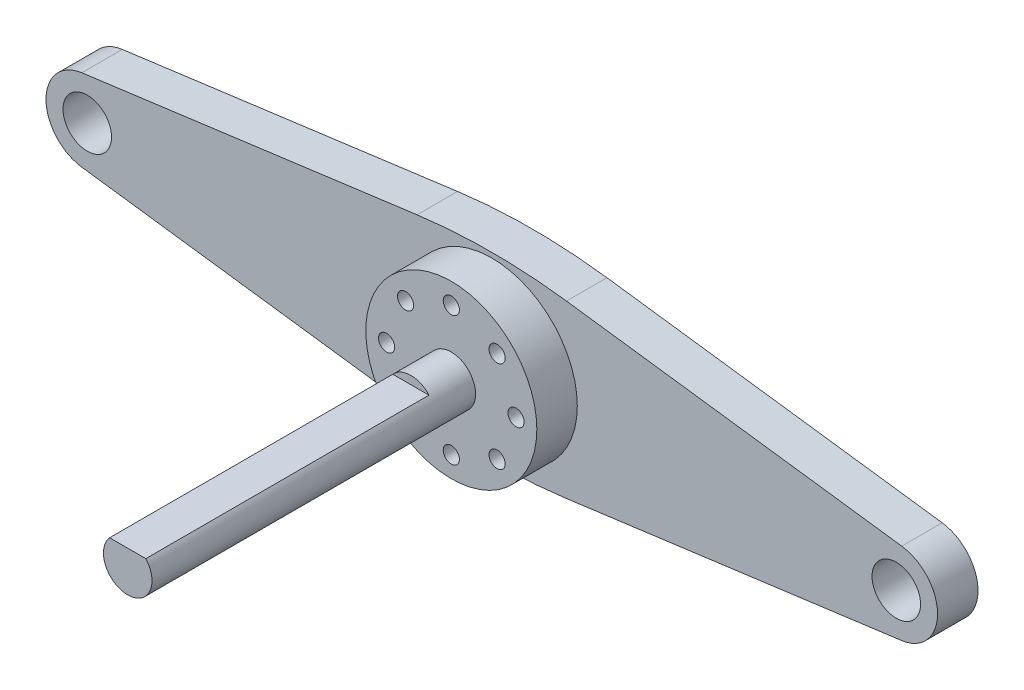
SolidWorks part; units mm, degrees
material "ABS"
ref_plane "Płaszczyzna przednia" through (0, 0, 0) normal (0, 0, 1) x (1, 0, 0)
ref_plane "Płaszczyzna górna" through (0, 0, 0) normal (0, 1, 0) x (1, 0, 0)
ref_plane "Płaszczyzna prawa" through (0, 0, 0) normal (1, 0, 0) x (0, 0, -1)
sketch "Szkic1" plane through (0, 0, 0) normal (0, 0, 1) x (1, 0, 0)
  line L0 (-44.521, 0) -> (57.4684, 0) construction
  line L1 (0, 0) -> (0, 26.3225) construction
  line L2 (-50.6729, 5.0557) -> (-9.2351, 10.5708)
  line L3 (-50.6729, -5.0557) -> (-9.2351, -10.5708)
  line L4 (50.6729, -5.0557) -> (9.2351, -10.5708)
  line L5 (50.6729, 5.0557) -> (9.2351, 10.5708)
  line L6 (2.2361, 2) -> (-2.2361, 2)
  circle A0 centre (0, 0) radius 3
  circle A1 centre (-5.6569, 5.6569) radius 1
  circle A2 centre (-8, 0) radius 1
  circle A3 centre (0, 8) radius 1
  circle A4 centre (5.6569, 5.6569) radius 1
  circle A5 centre (-50, 0) radius 3
  circle A6 centre (50, 0) radius 3
  arc A7 (-50.6729, 5.0557) -> (-50.6729, -5.0557) centre (-50, 0) ccw
  arc A8 (50.6729, 5.0557) -> (50.6729, -5.0557) centre (50, 0) cw
  arc A9 (-9.2351, 10.5708) -> (9.2351, 10.5708) centre (0, -58.8174) cw
  arc A10 (-9.2351, -10.5708) -> (9.2351, -10.5708) centre (0, 58.8174) ccw
  circle A11 centre (8, 0) radius 1
  circle A12 centre (5.6569, -5.6569) radius 1
  circle A13 centre (0, -8) radius 1
  circle A14 centre (-5.6569, -5.6569) radius 1
  circle A15 centre (0, 0) radius 10.5708
  point P16 (0, 0)
  point P28 (0, 11.7999)
  point P31 (0, -11.7999)
  point P41 (0, 0)
  dimension "D1" = 8
  dimension "D2" = 50
  dimension "D3" = 6
  dimension "D4" = 6
  dimension "D5" = 2
  dimension "D6" = 21.1415
  dimension "D7" = 70
  dimension "D8" = 5.1002
  dimension "D9" = 5.6569
  dimension "D10" = 9.2351
  dimension "D11" = 2
extrude "Dodanie-wyciągnięcie1" add sketch "Szkic1" along normal blind 5 contours L3 A10 L4 A8 L5 A9 L2 A7 A15 A6 A5 | A15 A0 A1 A2 A3 A4 A11 A12 A13 A14 | A0 region at (-29.8056, 6.6986, 0) region at (-10.2718, 0, 0)
extrude "Dodanie-wyciągnięcie2" add sketch "Szkic1<3>" along normal blind 10 contours A15 A0 A1 A2 A3 A4 A11 A12 A13 A14 region at (-10.2718, 0, 0)
sketch "Szkic1<3>" plane through (0, 0, 0) normal (0, 0, 1) x (1, 0, 0) same geometry as "Szkic1"
extrude "Dodanie-wyciągnięcie3" add sketch "Szkic1<4>" along normal blind 50 contours A0 region at (0, -0.296, 0)
sketch "Szkic1<4>" plane through (0, 0, 0) normal (0, 0, 1) x (1, 0, 0) same geometry as "Szkic1"
extrude "Dodanie-wyciągnięcie4" add sketch "Szkic1<5>" along normal blind 15 contours L6 A0 | L6 A0 region at (0, -0.296, 0) region at (0, 2.4063, 0)
sketch "Szkic1<5>" plane through (0, 0, 0) normal (0, 0, 1) x (1, 0, 0) same geometry as "Szkic1"
